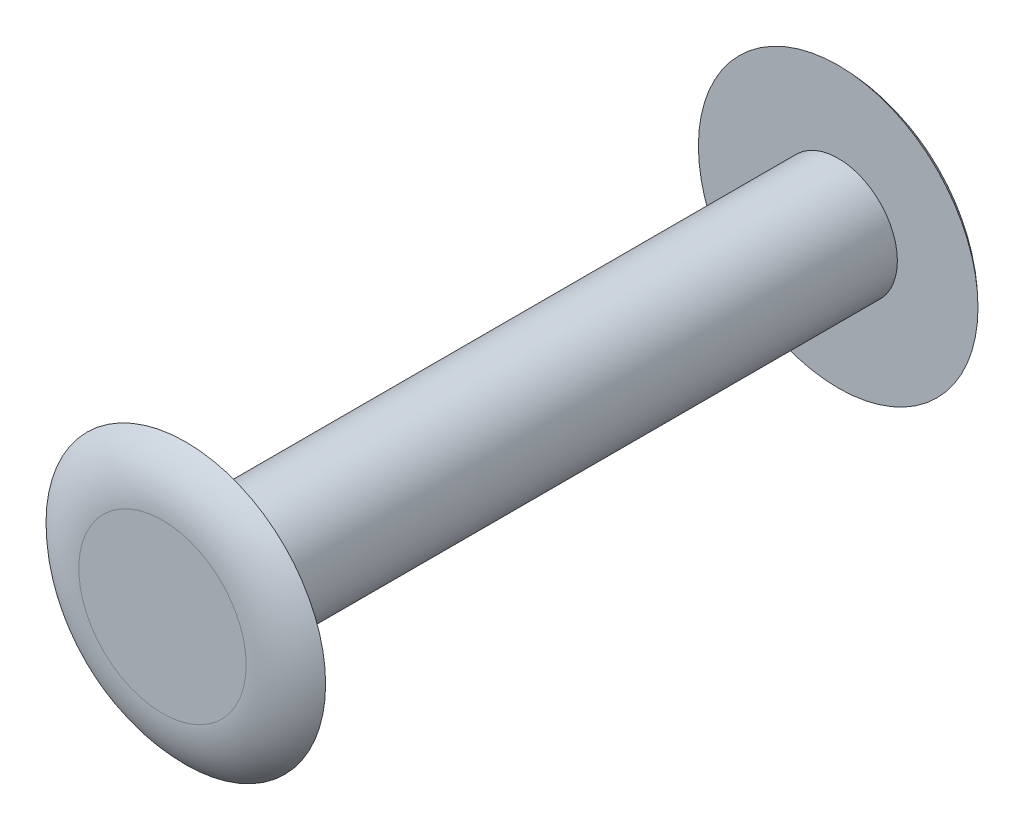
SolidWorks part; units mm, degrees
ref_plane "Front Plane" through (0, 0, 0) normal (0, 0, 1) x (1, 0, 0)
ref_plane "Top Plane" through (0, 0, 0) normal (0, 1, 0) x (1, 0, 0)
ref_plane "Right Plane" through (0, 0, 0) normal (1, 0, 0) x (0, 0, -1)
sketch "Sketch1" plane through (0, 0, 0) normal (0, 0, 1) x (1, 0, 0)
  circle A0 centre (0, 0) radius 6.35
  dimension "D1" = 12.7
extrude "Boss-Extrude1" add sketch "Sketch1" along normal blind 70
sketch "Sketch2" plane through (0, 0, 0) normal (0, 0, -1) x (-1, 0, 0)
  circle A3 centre (0, 0) radius 15
  dimension "D1" = 30
extrude "Boss-Extrude2" add sketch "Sketch2" along normal blind 2.5
sketch "Sketch3" plane through (0, 0, 70) normal (0, 0, 1) x (1, 0, 0)
  circle A3 centre (0, 0) radius 15
  dimension "D1" = 30
extrude "Boss-Extrude3" add sketch "Sketch3" along normal blind 2.5
fillet "Fillet1" radius 8.5 2 edges at (-15, 0, -2.5) (15, 0, 72.5)
